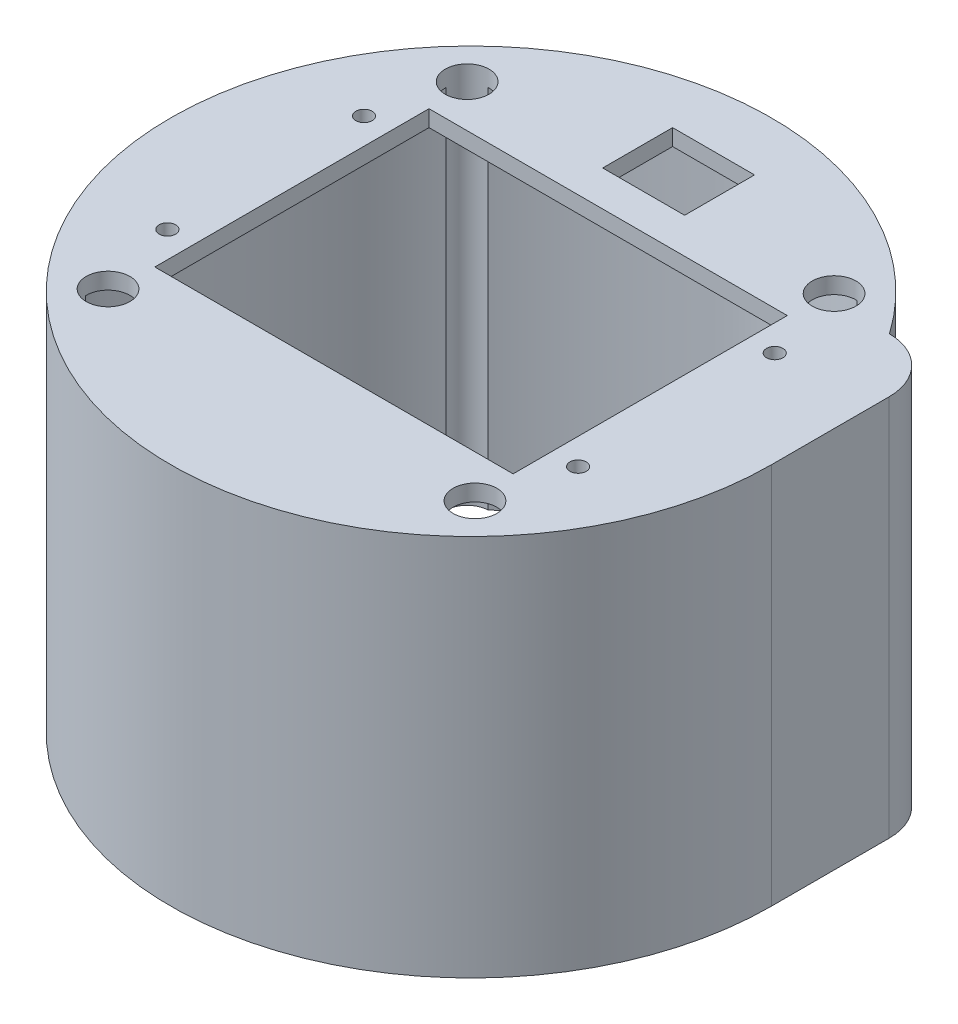
SolidWorks part; units mm, degrees
ref_plane "Спереди" through (0, 0, 0) normal (0, 0, 1) x (1, 0, 0)
ref_plane "Сверху" through (0, 0, 0) normal (0, 1, 0) x (1, 0, 0)
ref_plane "Справа" through (0, 0, 0) normal (1, 0, 0) x (0, 0, -1)
sketch "Эскиз1" plane through (0, 0, 0) normal (0, 1, 0) x (1, 0, 0)
  circle A0 centre (0, 0) radius 55
  dimension "D1" = 110
extrude "Бобышка-Вытянуть1" add sketch "Эскиз1" along normal blind 70
sketch "Эскиз2" plane through (0, 0, 0) normal (0, -1, 0) x (1, 0, 0)
  circle A0 centre (0, 0) radius 50
  dimension "D1" = 100
extrude "Вырез-Вытянуть1" cut sketch "Эскиз2" against normal blind 67
sketch "Эскиз3" plane through (0, 67, 0) normal (0, -1, 0) x (1, 0, 0)
  line L1 (-32.8, -25.1) -> (32.8, -25.1)
  line L2 (-32.8, -25.1) -> (-32.8, 25.1)
  line L3 (-32.8, 25.1) -> (32.8, 25.1)
  line L4 (32.8, -25.1) -> (32.8, 25.1)
  line L5 (-32.8, -25.1) -> (32.8, 25.1) construction
  line L6 (-32.8, 25.1) -> (32.8, -25.1) construction
  point P0 (0, 0)
  dimension "D1" = 50.2
  dimension "D2" = 65.6
extrude "Вырез-Вытянуть2" cut sketch "Эскиз3" against normal through all
sketch "Эскиз4" plane through (0, 70, 0) normal (0, 1, 0) x (1, 0, 0)
  line L0 (-32.8, 20.5) -> (-32.8, -20.5) construction
  line L1 (-32.8, -20.5) -> (32.8, -20.5) construction
  line L2 (32.8, -20.5) -> (32.8, 20.5) construction
  line L3 (32.8, 20.5) -> (-32.8, 20.5) construction
  line L4 (-23.35, 22.85) -> (23.35, 22.85) construction
  line L5 (32.8, -20.5) -> (-32.8, 20.5) construction
  line L6 (32.8, 20.5) -> (-32.8, -20.5) construction
  line L7 (23.35, 22.85) -> (23.35, -22.85) construction
  line L8 (39.3095, -38.4677) -> (-39.3095, 38.4677) construction
  line L9 (23.35, -22.85) -> (-23.35, -22.85) construction
  line L10 (-23.35, -22.85) -> (-23.35, 22.85) construction
  line L11 (32.8, 25.1) -> (32.8, -25.1) construction
  line L13 (23.35, -22.85) -> (-23.35, 22.85) construction
  line L14 (-32.8, -25.1) -> (-32.8, 25.1) construction
  line L15 (39.3095, 38.4677) -> (-39.3095, -38.4677) construction
  line L16 (23.35, 22.85) -> (-23.35, -22.85) construction
  circle A4 centre (0, 0) radius 55 construction
  circle A5 centre (33.5917, -32.8724) radius 4
  circle A6 centre (-33.5917, -32.8724) radius 4
  circle A7 centre (-33.5917, 32.8724) radius 4
  circle A8 centre (33.5917, 32.8724) radius 4
  point P0 (0, 0)
  point P5 (0, 0)
  point P27 (-32.8, 0)
  point P29 (32.8, 0)
  point P33 (-32.8, 0)
  dimension "D4" = 8
  dimension "D1" = 46.7
  dimension "D2" = 41
  dimension "D5" = 8
  dimension "D6" = 8
  dimension "D7" = 8
  dimension "D8" = 8
  dimension "D9" = 45.7
  dimension "D10" = 65.6
extrude "Вырез-Вытянуть3" cut sketch "Эскиз4" against normal through all
sketch "Sketch1" plane through (0, 0, 25.1) normal (0, 0, -1) x (-1, 0, 0)
  line L0 (0, 67) -> (0, 70) construction
  line L1 (-32.8, 67) -> (32.8, 67) construction
  line L2 (-32.8, 70) -> (32.8, 70) construction
  dimension "D1" = 3
sketch "Sketch2" plane through (0, 70, 0) normal (0, 1, 0) x (1, 0, 0)
  line L0 (-32.8, 0) -> (-37.6, 0) construction
  line L1 (-32.8, -25.1) -> (-32.8, 25.1) construction
  line L2 (-37.6, 0) -> (-37.6, 25.0956) construction
  line L3 (-37.6, 0) -> (-37.6, -25.0956) construction
  line L4 (32.8, 0) -> (37.6, 0) construction
  line L5 (32.8, 25.1) -> (32.8, -25.1) construction
  line L6 (37.6, 0) -> (37.6, -25.0956) construction
  line L7 (37.6, 0) -> (37.6, 25.0956) construction
  line L8 (37.6, 18) -> (-37.6, 18) construction
  line L9 (-37.6, -18) -> (37.6, -18) construction
  circle A1 centre (-37.6, 18) radius 1.5
  circle A2 centre (-37.6, -18) radius 1.5
  circle A3 centre (37.6, 18) radius 1.5
  circle A4 centre (37.6, -18) radius 1.5
  dimension "D4" = 3
  dimension "D1" = 4.8
  dimension "D2" = 36
  dimension "D3" = 18
extrude "Cut-Extrude1" cut sketch "Sketch2" against normal blind 10
sketch "Sketch3" plane through (0, 0, 0) normal (0, -1, 0) x (1, 0, 0)
  line L0 (40.9576, -28.6788) -> (45.0534, -31.5467)
  line L1 (50, 0) -> (55, 0)
  line L2 (55, 0) -> (0, 0) construction
  line L3 (0, 0) -> (45.0534, -31.5467) construction
  line L4 (0, 0) -> (0, -55) construction
  arc A0 (50, 0) -> (40.9576, -28.6788) centre (0, 0) cw
  arc A1 (55, 0) -> (45.0534, -31.5467) centre (0, 0) cw
  arc A2 (37.5906, -32.9689) -> (37.5906, 32.9689) centre (0, 0) ccw construction
  circle A3 centre (0, 0) radius 55 construction
  dimension "D1" = 90
  dimension "D2" = 55
extrude "Cut-Extrude2" cut sketch "Sketch3" against normal up to surface (67 mm away) up to face at (-37.6, 67, 16.5)
sketch "Sketch5" plane through (0, 67, 0) normal (0, -1, 0) x (1, 0, 0)
  line L0 (45.0534, -31.5467) -> (78.4523, -31.5467) construction
  line L1 (55, 0) -> (55, -31.5467)
  line L2 (55, -31.5467) -> (45.0534, -31.5467)
  line L3 (55, 0) -> (50, 0)
  line L4 (50, 0) -> (50, -28.6788)
  line L5 (50, -28.6788) -> (40.9576, -28.6788)
  line L6 (40.9576, -28.6788) -> (45.0534, -31.5467)
extrude "Boss-Extrude1" add sketch "Sketch5" along normal up to surface (67 mm away) up to face at (6.5982, 0, -2.2359)
sketch "Sketch6" plane through (0, 67, 0) normal (0, 1, 0) x (1, 0, 0)
  line L0 (55, 0) -> (55, 31.5467)
  line L1 (55, 31.5467) -> (45.0534, 31.5467)
  arc A0 (55, 0) -> (45.0534, 31.5467) centre (0, 0) ccw
extrude "Boss-Extrude2" add sketch "Sketch6" along normal up to surface (3 mm away) up to face at (-37.6, 70, 19.5)
fillet "Fillet1" radius 10 1 edges at (55, 35, -31.5467)
fillet "Fillet2" radius 2 1 edges at (50, 33.5, -28.6788)
sketch "Sketch8" plane through (0, 70, 0) normal (0, 1, 0) x (1, 0, 0)
  line L0 (-39.7618, 38) -> (39.7618, 38) construction
  line L2 (7.5, 44.4) -> (-7.5, 44.4)
  line L3 (7.5, 44.4) -> (7.5, 31.6)
  line L4 (7.5, 31.6) -> (-7.5, 31.6)
  line L5 (-7.5, 44.4) -> (-7.5, 31.6)
  line L6 (7.5, 44.4) -> (-7.5, 31.6) construction
  line L7 (7.5, 31.6) -> (-7.5, 44.4) construction
  arc A0 (45.0534, 31.5467) -> (55, 0) centre (0, 0) ccw construction
  point P5 (0, 38)
  dimension "D1" = 15
  dimension "D2" = 12.8
  dimension "D3" = 38
extrude "Cut-Extrude3" cut sketch "Sketch8" against normal through all
